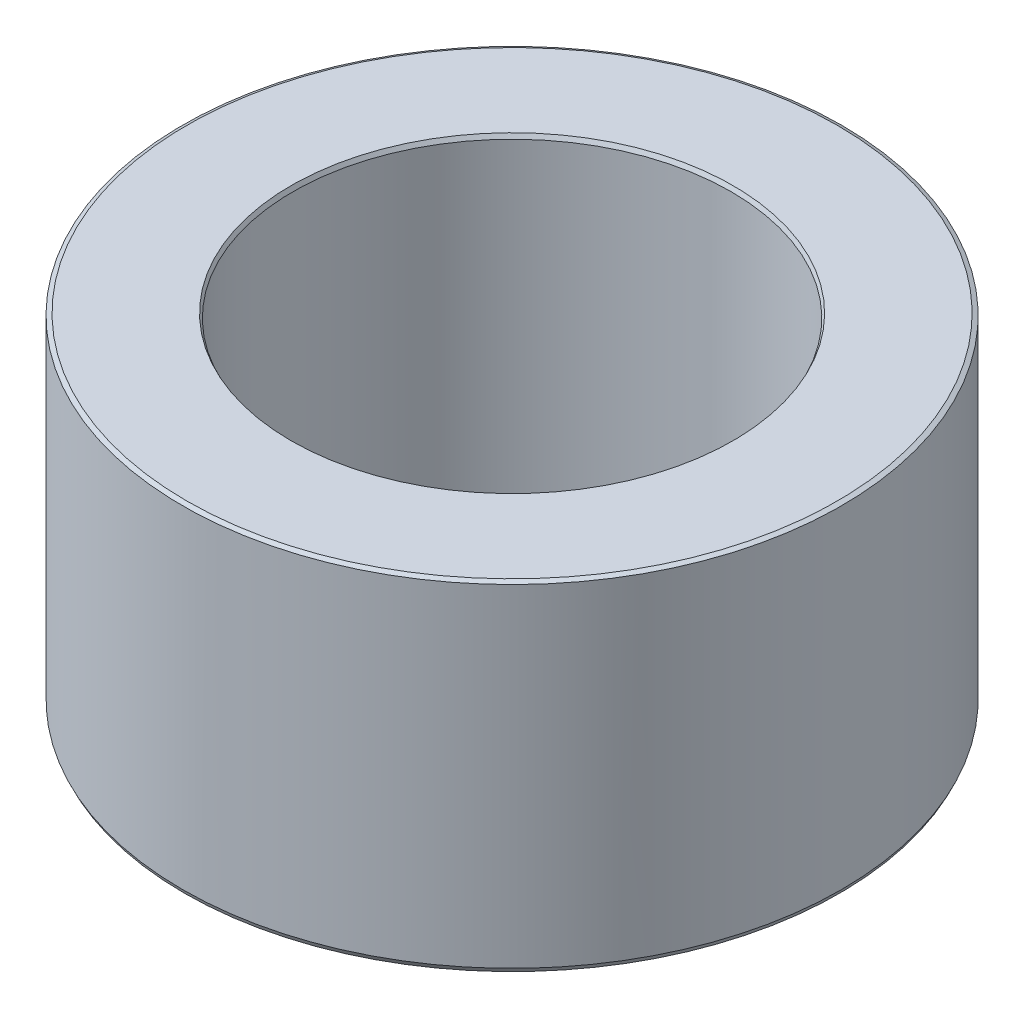
SolidWorks part; units mm, degrees
ref_plane "Front Plane" through (0, 0, 0) normal (0, 0, 1) x (1, 0, 0)
ref_plane "Top Plane" through (0, 0, 0) normal (0, 1, 0) x (1, 0, 0)
ref_plane "Right Plane" through (0, 0, 0) normal (1, 0, 0) x (0, 0, -1)
sketch "Sketch1" plane through (0, 0, 0) normal (0, 1, 0) x (1, 0, 0)
  circle A0 centre (0, 0) radius 40
  dimension "SLEEVE_OD" = 80
extrude "Boss-Extrude1" add sketch "Sketch1" along normal blind 41.0966
sketch "Sketch2" plane through (0, 0, 0) normal (0, 1, 0) x (1, 0, 0)
  circle A0 centre (0, 0) radius 26.5839
  dimension "BORE_D" = 53.1679
extrude "Cut-Extrude1" cut sketch "Sketch2" along normal through all
chamfer "Chamfer1" distance 0.2404 angle 64.956 4 edges at (0, 41.0966, 26.5839) (0, 0, 26.5839) (0, 0, 40) (0, 41.0966, 40) first distance on face at (0, 41.0966, 26.5839) first distance on face at (0, 0, 26.5839) first distance on face at (0, 41.0966, 40)
